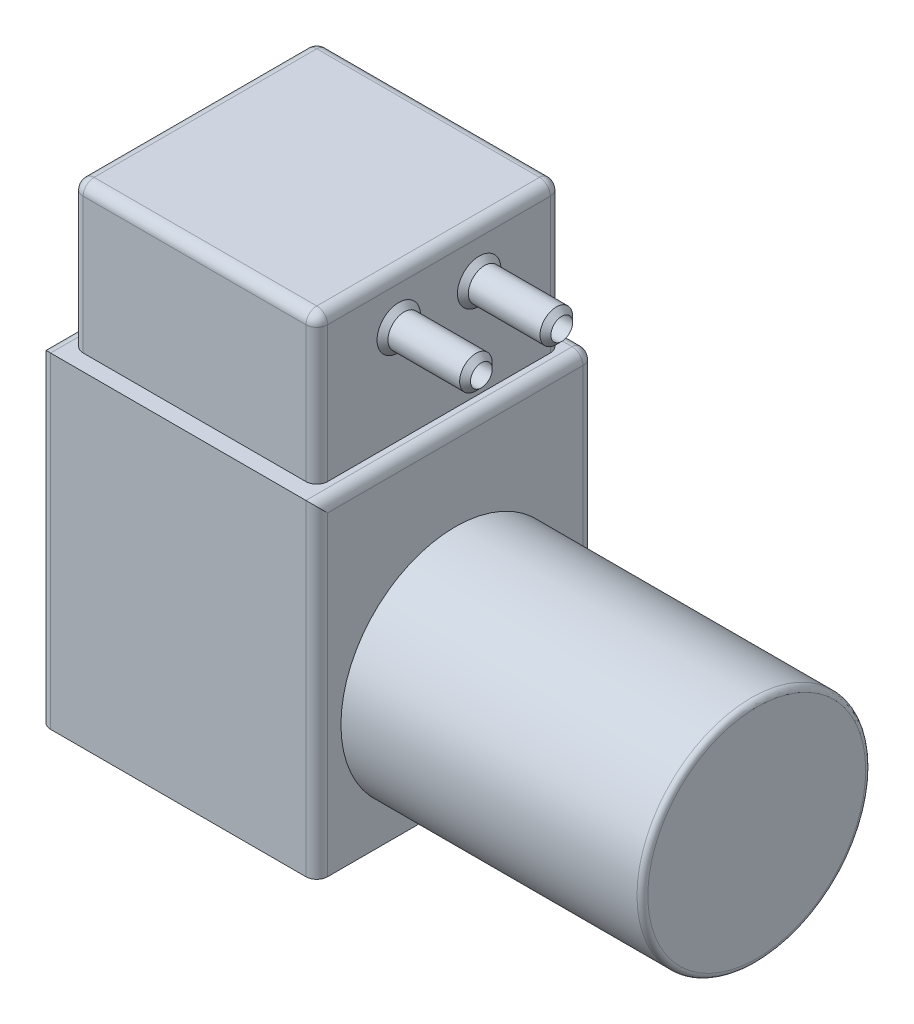
SolidWorks part; units mm, degrees
ref_plane "Plan de face" through (0, 0, 0) normal (0, 0, 1) x (1, 0, 0)
ref_plane "Plan de dessus" through (0, 0, 0) normal (0, 1, 0) x (1, 0, 0)
ref_plane "Plan de droite" through (0, 0, 0) normal (1, 0, 0) x (0, 0, -1)
sketch "Esquisse1" plane through (0, 0, 0) normal (0, 1, 0) x (1, 0, 0)
  line L1 (0, 0) -> (51, 0)
  line L2 (0, 0) -> (0, 51)
  line L3 (0, 51) -> (51, 51)
  line L4 (51, 0) -> (51, 51)
  dimension "D1" = 51
  dimension "D2" = 51
extrude "Boss.-Extru.1" add sketch "Esquisse1" along normal blind 60
sketch "Esquisse2" plane through (0, 60, 0) normal (0, 1, 0) x (1, 0, 0)
  line L0 (0, 0) -> (51, 0) construction
  line L1 (3, 48) -> (48, 48)
  line L2 (3, 48) -> (3, 3)
  line L3 (3, 3) -> (48, 3)
  line L4 (48, 48) -> (48, 3)
  line L5 (0, 51) -> (0, 0) construction
  dimension "D1" = 45
  dimension "D2" = 45
  dimension "D3" = 3
  dimension "D4" = 3
extrude "Boss.-Extru.2" add sketch "Esquisse2" along normal blind 27
sketch "Esquisse3" plane through (51, 0, 0) normal (1, 0, 0) x (0, 0, -1)
  line L0 (51, 60) -> (51, 0) construction
  line L1 (0, 0) -> (51, 0) construction
  circle A0 centre (25.5, 23) radius 21.05
  dimension "D1" = 25.5
  dimension "D3" = 42.1
  dimension "D2" = 23
extrude "Boss.-Extru.3" add sketch "Esquisse3" along normal blind 55.5
sketch "Esquisse4" plane through (48, 0, 0) normal (1, 0, 0) x (0, 0, -1)
  line L0 (3, 60) -> (48, 60) construction
  line L1 (3, 87) -> (3, 60) construction
  circle A0 centre (18.1, 78) radius 4
  circle A1 centre (32.9, 78) radius 4
  dimension "D2" = 8
  dimension "D3" = 8
  dimension "D1" = 14.8
  dimension "D4" = 18
  dimension "D5" = 15.1
  dimension "D6" = 18
extrude "Boss.-Extru.4" add sketch "Esquisse4" along normal blind 1
sketch "Esquisse5" plane through (49, 0, 0) normal (1, 0, 0) x (0, 0, -1)
  circle A0 centre (18.1, 78) radius 3
  circle A1 centre (32.9, 78) radius 3
  circle A2 centre (32.9, 78) radius 4 construction
  circle A3 centre (18.1, 78) radius 4 construction
  circle A4 centre (18.1, 78) radius 2
  circle A5 centre (32.9, 78) radius 2
  dimension "D1" = 6
  dimension "D2" = 6
  dimension "D3" = 4
  dimension "D4" = 4
extrude "Boss.-Extru.5" add sketch "Esquisse5" along normal blind 14.2
chamfer "Chanfrein1" distance 1 angle 45 4 edges at (63.2, 78, -35.9) (49, 78, -36.9) (63.2, 78, -21.1) (49, 78, -22.1)
fillet "Congé1" radius 2 8 edges at (3, 73.5, -3) (3, 73.5, -48) (48, 73.5, -48) (25.5, 87, -48) (3, 87, -25.5) (48, 87, -25.5) (48, 73.5, -3) (25.5, 87, -3)
fillet "Congé2" radius 2 7 edges at (51, 30, 0) (0, 30, 0) (0, 60, -25.5) (0, 30, -51) (25.5, 60, -51) (51, 30, -51) (51, 60, -25.5)
fillet "Congé3" radius 1 1 edges at (106.5, 23, -46.55)
